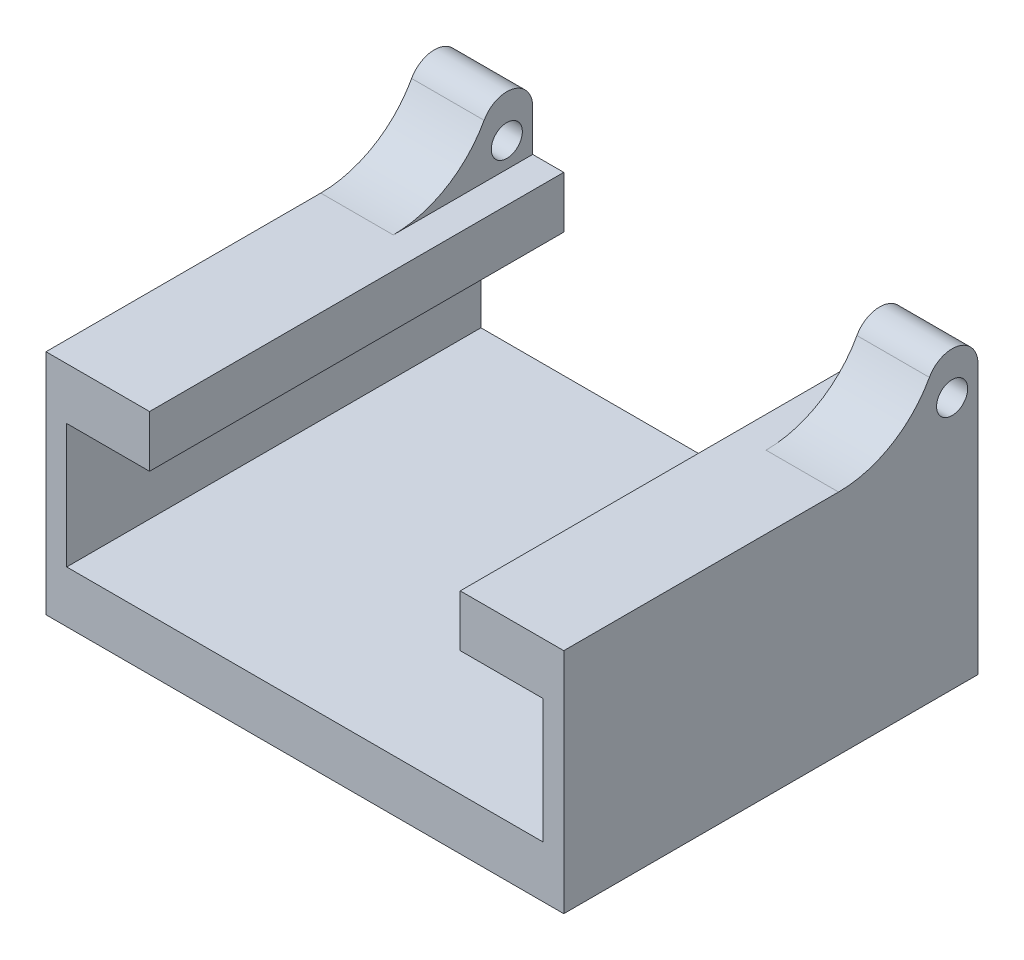
SolidWorks part; units mm, degrees
ref_plane "Front Plane" through (0, 0, 0) normal (0, 0, 1) x (1, 0, 0)
ref_plane "Top Plane" through (0, 0, 0) normal (0, 1, 0) x (1, 0, 0)
ref_plane "Right Plane" through (0, 0, 0) normal (1, 0, 0) x (0, 0, -1)
sketch "Sketch1" plane through (0, 0, 0) normal (0, 1, 0) x (1, 0, 0)
  line L1 (0, 0) -> (50, 0)
  line L2 (0, 0) -> (0, 40)
  line L3 (0, 40) -> (50, 40)
  line L4 (50, 0) -> (50, 40)
  dimension "D1" = 50
  dimension "D2" = 40
extrude "Boss-Extrude2" add sketch "Sketch1" along normal blind 5 contours L2 L3 L4 L1
sketch "Sketch2" plane through (0, 5, 0) normal (0, 1, 0) x (1, 0, 0)
  line L0 (0, 0) -> (50, 0) construction
  line L1 (0, 40) -> (2, 40)
  line L2 (0, 40) -> (0, 0)
  line L3 (0, 0) -> (2, 0)
  line L4 (2, 40) -> (2, 0)
  line L6 (50, 40) -> (48, 40)
  line L7 (50, 40) -> (50, 0)
  line L8 (50, 0) -> (48, 0)
  line L9 (48, 40) -> (48, 0)
  dimension "D1" = 2
  dimension "D2" = 2
extrude "Boss-Extrude4" add sketch "Sketch2" along normal blind 12
sketch "Sketch3" plane through (0, 17, 0) normal (0, 1, 0) x (1, 0, 0)
  line L1 (0, 40) -> (10, 40)
  line L2 (0, 40) -> (0, 0)
  line L3 (0, 0) -> (10, 0)
  line L4 (10, 40) -> (10, 0)
  line L5 (50, 40) -> (40, 40)
  line L6 (50, 40) -> (50, 0)
  line L7 (50, 0) -> (40, 0)
  line L8 (40, 40) -> (40, 0)
  dimension "D1" = 10
  dimension "D2" = 10
extrude "Boss-Extrude5" add sketch "Sketch3" along normal blind 5
ref_plane "Plane1" through (0, 0, -35) normal (0, 0, 1) x (1, 0, 0)
sketch "Sketch5" plane through (0, 0, 0) normal (-1, 0, 0) x (0, 0, 1)
  line L0 (-35, -12.1) -> (-35, 12.1) construction
  line L1 (-40, 22) -> (-35, 22)
  line L2 (-40, 22) -> (-40, 26)
  line L4 (-35, 22) -> (-35, 26)
  arc A0 (-40, 26) -> (-35, 26) centre (-37.5, 26) cw
  circle A1 centre (-37.5, 24.4146) radius 1.5
  dimension "D3" = 3
  dimension "D1" = 5
  dimension "D2" = 4
extrude "Boss-Extrude6" add sketch "Sketch5" against normal blind 7
fillet "Fillet1" radius 10 1 edges at (3.5, 22, -35)
ref_plane "Plane2" through (25, 0, 0) normal (1, 0, 0) x (0, 0, -1)
sketch "Sketch6" plane through (50, 0, 0) normal (1, 0, 0) x (0, 0, -1)
  line L0 (35, 22) -> (40, 22)
  line L1 (35, 22) -> (35, 26)
  line L2 (40, 22) -> (40, 26)
  arc A0 (35, 26) -> (40, 26) centre (37.5, 26) cw
  circle A1 centre (37.5, 24.4146) radius 1.5
extrude "Boss-Extrude7" add sketch "Sketch6" against normal blind 7
fillet "Fillet2" radius 10 1 edges at (46.5, 22, -35)
